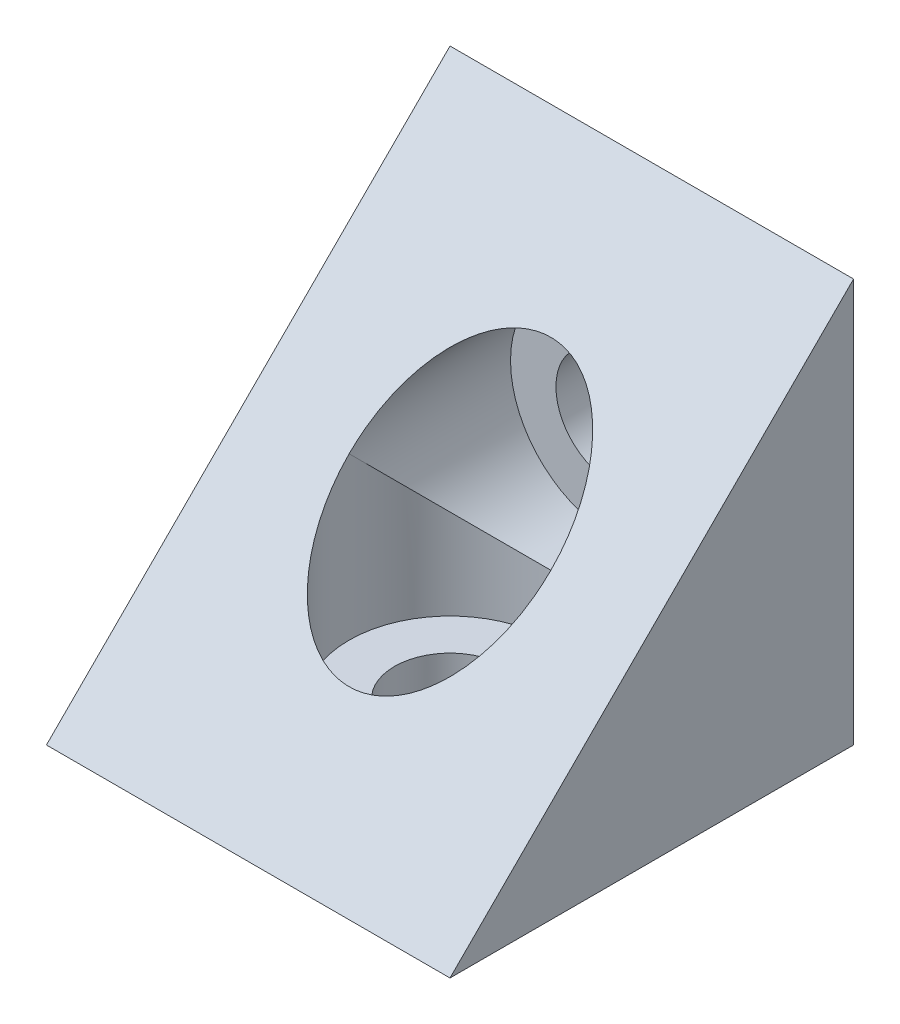
SolidWorks part; units mm, degrees
material "1060 Alloy"
ref_plane "Top Plane" through (0, 0, 0) normal (0, 0, 1) x (1, 0, 0)
ref_plane "Front Plane" through (0, 0, 0) normal (0, 1, 0) x (1, 0, 0)
ref_plane "Right Plane" through (0, 0, 0) normal (1, 0, 0) x (0, 0, -1)
sketch "Sketch1" plane through (0, 0, 0) normal (1, 0, 0) x (0, 0, -1)
  line L0 (0, 0) -> (0, 20)
  line L1 (0, 0) -> (-20, 0)
  line L2 (0, 20) -> (-20, 0)
  dimension "D1" = 20
  dimension "D2" = 20
extrude "corner base" add sketch "Sketch1" along normal blind 10 and the other way blind 10
sketch "Sketch2" plane through (0, 0, 0) normal (0, -1, 0) x (1, 0, 0)
  circle A0 centre (0, 10) radius 2.75
  dimension "D2" = 5.5
  dimension "D1" = 10
extrude "screw shaft 1" cut sketch "Sketch2" against normal through all
sketch "Sketch3" plane through (0, 0, 0) normal (0, 0, -1) x (-1, 0, 0)
  circle A0 centre (0, 10) radius 2.75
  dimension "D2" = 5.5
  dimension "D1" = 10
extrude "screw shaft 2" cut sketch "Sketch3" against normal through all
ref_plane "Plane1" through (0, 0, 2) normal (0, 0, 1) x (1, 0, 0)
sketch "Sketch4" plane through (0, 0, 2) normal (0, 0, 1) x (1, 0, 0)
  circle A0 centre (0, 10) radius 5
  dimension "D1" = 10
  dimension "D2" = 10
extrude "screw socket 1" cut sketch "Sketch4" along normal through all
ref_plane "Plane2" through (0, 2, 0) normal (0, 1, 0) x (1, 0, 0)
sketch "Sketch5" plane through (0, 2, 0) normal (0, 1, 0) x (1, 0, 0)
  circle A0 centre (0, -10) radius 5
  dimension "D2" = 10
  dimension "D1" = 10
extrude "Cut-Extrude4" cut sketch "Sketch5" along normal through all
